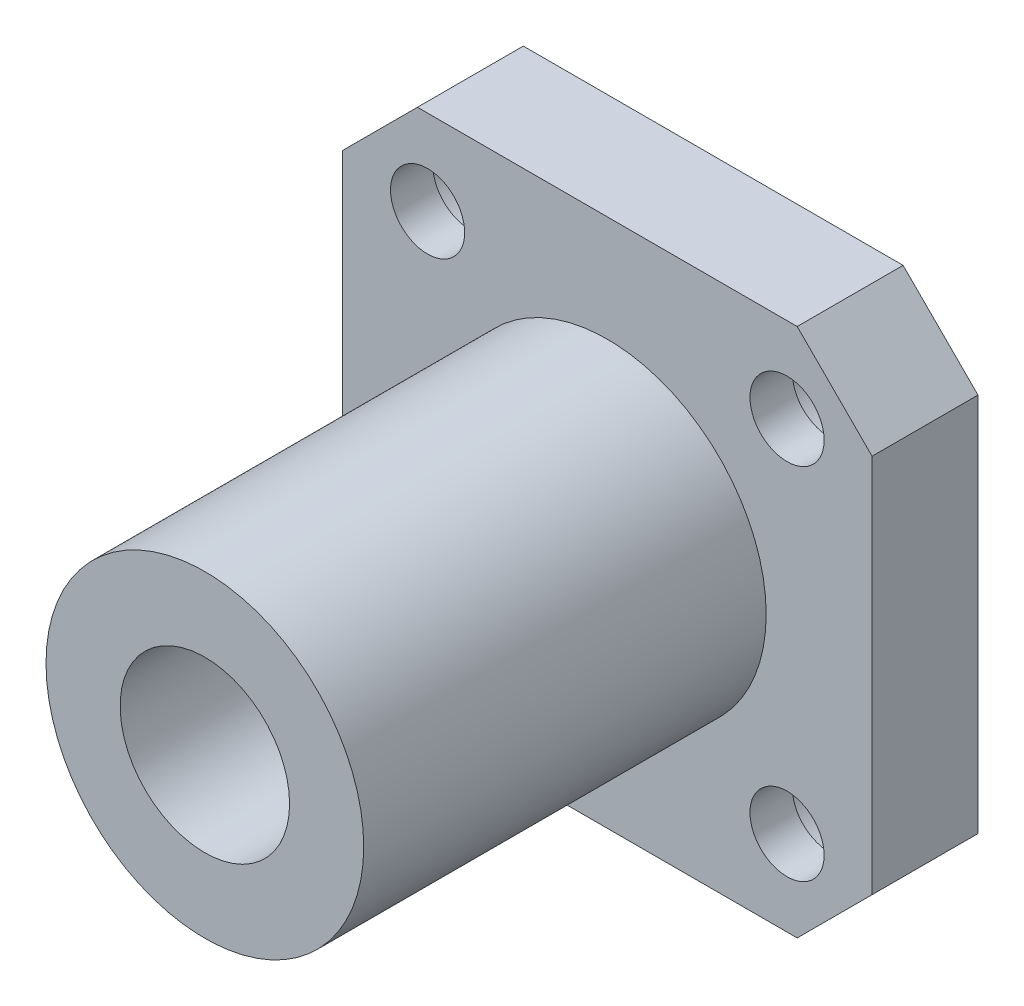
SolidWorks part; units mm, degrees
ref_plane "Front Plane" through (0, 0, 0) normal (0, 0, 1) x (1, 0, 0)
ref_plane "Top Plane" through (0, 0, 0) normal (0, 1, 0) x (1, 0, 0)
ref_plane "Right Plane" through (0, 0, 0) normal (1, 0, 0) x (0, 0, -1)
sketch "Sketch2" plane through (0, 0, 0) normal (0, 0, 1) x (1, 0, 0)
  line L0 (-12.5, 12.5) -> (12.5, -12.5) construction
  line L1 (-8.9645, 12.5) -> (8.9645, 12.5)
  line L2 (-12.5, 8.9645) -> (-12.5, -8.9645)
  line L3 (-8.9645, -12.5) -> (8.9645, -12.5)
  line L4 (12.5, 8.9645) -> (12.5, -8.9645)
  line L5 (-12.5, 8.9645) -> (-8.9645, 12.5)
  line L6 (-12.5, 12.5) -> (-12.5, 8.9645) construction
  line L7 (-12.5, 12.5) -> (-8.9645, 12.5) construction
  line L8 (8.9645, -12.5) -> (12.5, -8.9645)
  line L9 (8.9645, -12.5) -> (12.5, -12.5) construction
  line L10 (12.5, -8.9645) -> (12.5, -12.5) construction
  line L11 (-12.5, -8.9645) -> (-8.9645, -12.5)
  line L12 (8.9645, 12.5) -> (12.5, 8.9645)
  line L13 (8.9645, 12.5) -> (12.5, 12.5) construction
  line L14 (12.5, 12.5) -> (12.5, 8.9645) construction
  line L15 (-12.5, -8.9645) -> (-12.5, -12.5) construction
  line L16 (-12.5, -12.5) -> (-8.9645, -12.5) construction
  line L17 (-8.4853, 8.4853) -> (8.4853, -8.4853) construction
  line L18 (-8.4853, -8.4853) -> (8.4853, 8.4853) construction
  circle A0 centre (-8.4853, 8.4853) radius 1.75
  circle A1 centre (8.4853, -8.4853) radius 1.75
  circle A2 centre (8.4853, 8.4853) radius 1.75
  circle A3 centre (-8.4853, -8.4853) radius 1.75
  circle A4 centre (0, 0) radius 4
  dimension "D5" = 3.5
  dimension "D7" = 8
  dimension "D1" = 25
  dimension "D2" = 25
  dimension "D3" = 5
  dimension "D4" = 24
  dimension "D6" = 24
extrude "Boss-Extrude1" add sketch "Sketch2" along normal blind 5
sketch "Sketch3" plane through (0, 0, 5) normal (0, 0, 1) x (1, 0, 0)
  circle A0 centre (0, 0) radius 7.5
  circle A1 centre (0, 0) radius 4
  dimension "D1" = 15
  dimension "D2" = 8
extrude "Boss-Extrude2" add sketch "Sketch3" along normal blind 19
ref_axis "Z" through (0, 0, -1.2) along (0, 0, 1)
sketch "Sketch4" plane through (0, 0, 0) normal (0, 0, -1) x (-1, 0, 0)
  circle A0 centre (-8.4853, 8.4853) radius 2.8
  circle A1 centre (8.4853, -8.4853) radius 1.75 construction
  circle A2 centre (-8.4853, 8.4853) radius 1.75 construction
  circle A3 centre (8.4853, 8.4853) radius 2.8
  circle A4 centre (8.4853, -8.4853) radius 2.8
  circle A5 centre (-8.4853, -8.4853) radius 2.8
  circle A6 centre (-8.4853, -8.4853) radius 1.75 construction
  circle A8 centre (8.4853, 8.4853) radius 1.75 construction
  dimension "D1" = 5.6
extrude "Cut-Extrude1" cut sketch "Sketch4" against normal blind 3
